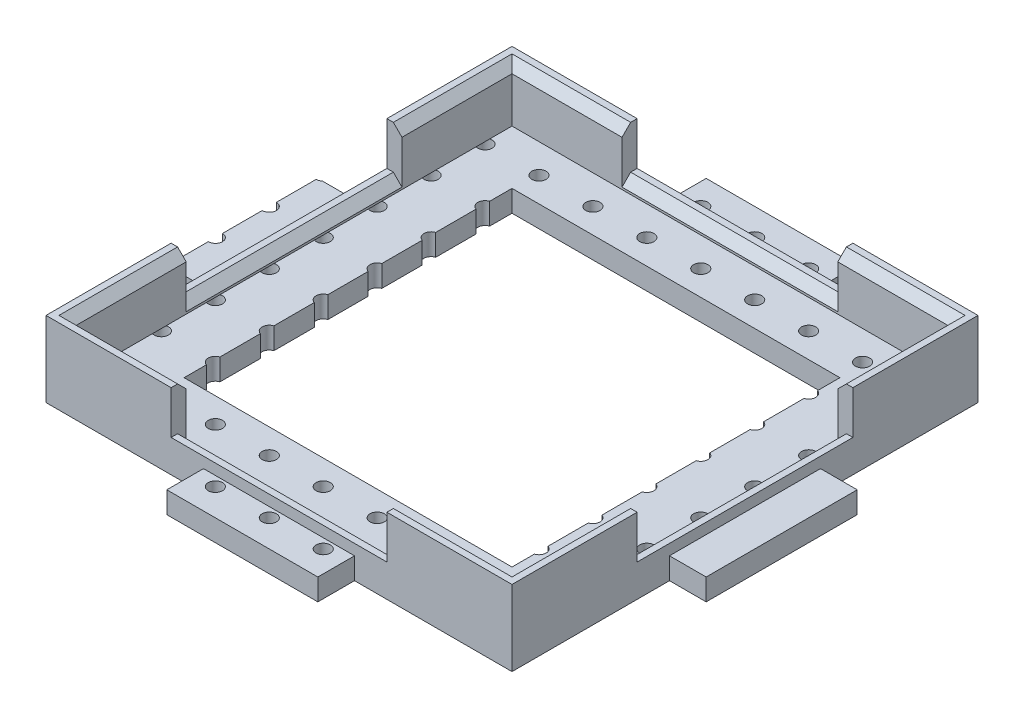
SolidWorks part; units mm, degrees
note: '?' marks a value the reader was unsure of.
ref_plane "Front Plane" through (0, 0, 0) normal (0, 0, 1) x (1, 0, 0)
ref_plane "Top Plane" through (0, 0, 0) normal (0, 1, 0) x (1, 0, 0)
ref_plane "Right Plane" through (0, 0, 0) normal (1, 0, 0) x (0, 0, -1)
sketch "Sketch1" plane through (0, 0, 0) normal (0, 1, 0) x (1, 0, 0)
  line L0 (0, 101) -> (0, 108) construction
  line L1 (-101, 101) -> (101, 101)
  line L2 (-101, 101) -> (-101, -101)
  line L3 (-101, -101) -> (101, -101)
  line L4 (101, 101) -> (101, -101)
  line L5 (-101, 101) -> (101, -101) construction
  line L6 (-101, -101) -> (101, 101) construction
  line L7 (-108, 108) -> (108, 108)
  line L8 (-108, 108) -> (-108, -108)
  line L9 (-108, -108) -> (108, -108)
  line L10 (108, 108) -> (108, -108)
  line L11 (-108, 108) -> (108, -108) construction
  line L12 (-108, -108) -> (108, 108) construction
  line L13 (101, 0) -> (108, 0) construction
  point P0 (0, 0)
  point P6 (0, 0)
  dimension "D1" = 202
  dimension "D2" = 202
  dimension "D3" = 7
extrude "Boss-Extrude1" add sketch "Sketch1" along normal blind 25
sketch "Sketch3" plane through (0, 0, 0) normal (0, 0, 1) x (1, 0, 0)
  line L0 (-108, 25) -> (108, 25) construction
  line L1 (50, 25) -> (-50, 25)
  line L2 (50, 25) -> (50, 5)
  line L3 (50, 5) -> (-50, 5)
  line L4 (-50, 25) -> (-50, 5)
  line L5 (-108, 0) -> (108, 0) construction
  point P9 (0, 5)
  dimension "D1" = 5
  dimension "D2" = 100
extrude "Cut-Extrude1" cut sketch "Sketch3" along normal through all
sketch "Sketch2" plane through (0, 0, 0) normal (0, 1, 0) x (1, 0, 0)
  line L0 (0, 76) -> (0, 101) construction
  line L1 (-101, -101) -> (101, -101) construction
  line L2 (-101, -101) -> (-101, 101) construction
  line L3 (-101, 101) -> (101, 101) construction
  line L4 (101, -101) -> (101, 101) construction
  line L5 (-101, -101) -> (101, 101) construction
  line L6 (-101, 101) -> (101, -101) construction
  line L7 (-76, -76) -> (76, -76)
  line L8 (-76, -76) -> (-76, 76)
  line L9 (-76, 76) -> (76, 76)
  line L10 (76, -76) -> (76, 76)
  line L11 (-76, -76) -> (76, 76) construction
  line L12 (-76, 76) -> (76, -76) construction
  line L13 (76, 0) -> (101, 0) construction
  line L15 (-108, -108) -> (108, -108)
  line L16 (-108, -108) -> (-108, 108)
  line L17 (-108, 108) -> (108, 108)
  line L18 (108, -108) -> (108, 108)
  line L19 (-108, -108) -> (108, 108) construction
  line L20 (-108, 108) -> (108, -108) construction
  point P0 (0, 0)
  point P7 (0, 0)
  point P16 (0, 0)
  dimension "D1" = 25
extrude "Boss-Extrude2" add sketch "Sketch2" against normal blind 10 from surface at 0 starting at face at (0, 0, 0)
sketch "Sketch4" plane through (0, 0, 0) normal (0, 1, 0) x (1, 0, 0)
  line L0 (-50, -108) -> (50, -108) construction
  line L5 (35, -108) -> (-35, -108)
  line L10 (35, -108) -> (35, -125)
  line L11 (35, -125) -> (-35, -125)
  line L12 (-35, -108) -> (-35, -125)
  point P6 (0, -108)
  dimension "D1" = 70
  dimension "D2" = 125
extrude "Boss-Extrude3" add sketch "Sketch4" against normal up to surface (10 mm away) up to face at (0, -10, 0)
sketch "Sketch5" plane through (0, 0, 0) normal (0, 1, 0) x (1, 0, 0)
  line L0 (-25, -112.5) -> (25, -112.5) construction
  line L1 (0, -112.5) -> (0, 0) construction
  circle A0 centre (-25, -112.5) radius 3.3
  circle A1 centre (25, -112.5) radius 3.3 construction
  dimension "D1" = 6.6
  dimension "D2" = 112.5
  dimension "D3" = 50
extrude "Cut-Extrude2" cut sketch "Sketch5" against normal through all
ref_axis "Axis1" through (0, 26.75, 0) along (0, -1, 0)?
pattern_circular "CirPattern1" count 4 over 360 about axis through (0, 0, 0) along (0, 1, 0) of "Boss-Extrude3", "Cut-Extrude1"
pattern_linear "LPattern1" count 11 spacing 25 along (0, 0, -1) of "Cut-Extrude2"
pattern_linear "LPattern2" count 5 spacing 25 along (-1, 0, 0) count 6 spacing 25 along (1, 0, 0) of "LPattern1", "Cut-Extrude2"
chamfer "Chamfer1" distance 4 angle 45 12 edges at (101, 5, 0) (0, 5, -101) (101, 25, 75.5) (75.5, 25, -101) (-101, 25, -75.5) (-75.5, 25, 101) (75.5, 25, 101) (0, 5, 101) (-101, 25, 75.5) (-101, 5, 0) (-75.5, 25, -101) (101, 25, -75.5)
